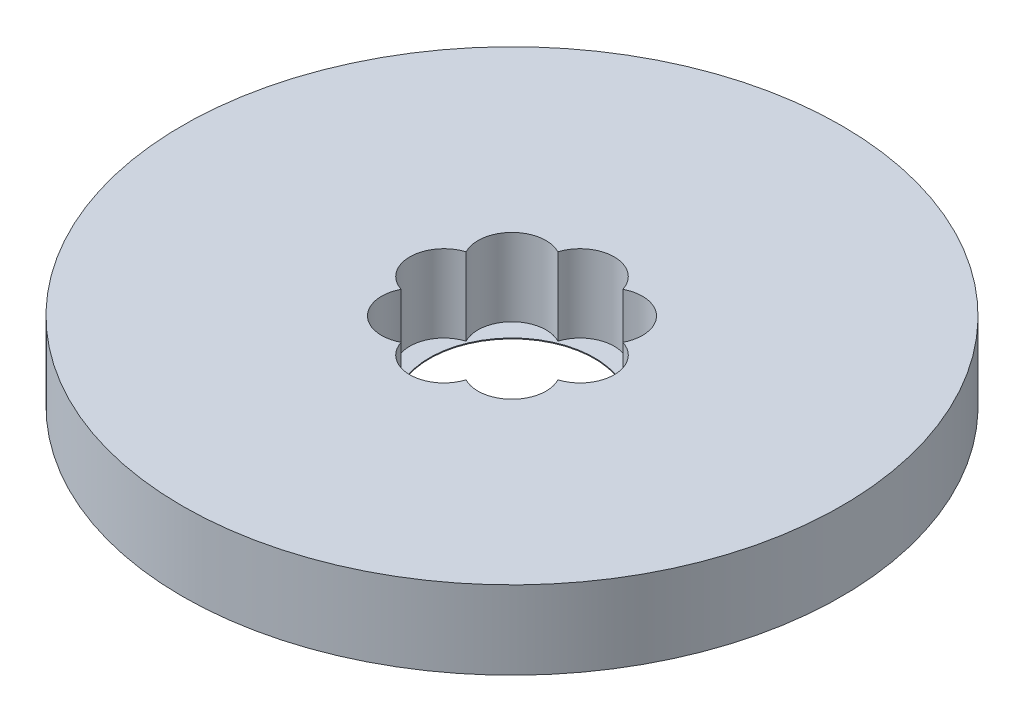
SolidWorks part; units mm, degrees
ref_plane "Front Plane" through (0, 0, 0) normal (0, 0, 1) x (1, 0, 0)
ref_plane "Top Plane" through (0, 0, 0) normal (0, 1, 0) x (1, 0, 0)
ref_plane "Right Plane" through (0, 0, 0) normal (1, 0, 0) x (0, 0, -1)
sketch "Sketch1" plane through (0, 0, 0) normal (0, 1, 0) x (1, 0, 0)
  circle A0 centre (0, 0) radius 80
  dimension "FLANGE_OD" = 160
extrude "Boss-Extrude1" add sketch "Sketch1" along normal blind 19
sketch "Sketch2" plane through (0, 0, 0) normal (0, 1, 0) x (1, 0, 0)
  circle A0 centre (0, 0) radius 20
  dimension "BORE_D" = 40
extrude "Cut-Extrude1" cut sketch "Sketch2" along normal through all
sketch "Sketch3" plane through (0, 19, 0) normal (0, 1, 0) x (1, 0, 0)
  circle A0 centre (0, 0) radius 16.5365 construction
  circle A1 centre (-16.5365, 0) radius 8.2712
  dimension "BOLT_D" = 16.5425
  dimension "BOLT_PCD" = 33.073
extrude "Cut-Extrude2" cut sketch "Sketch3" against normal blind 18.7904
pattern_circular "CirPattern1" count 8 over 360 about axis through (0, 0, 0) along (0, 1, 0) of "Cut-Extrude2"
